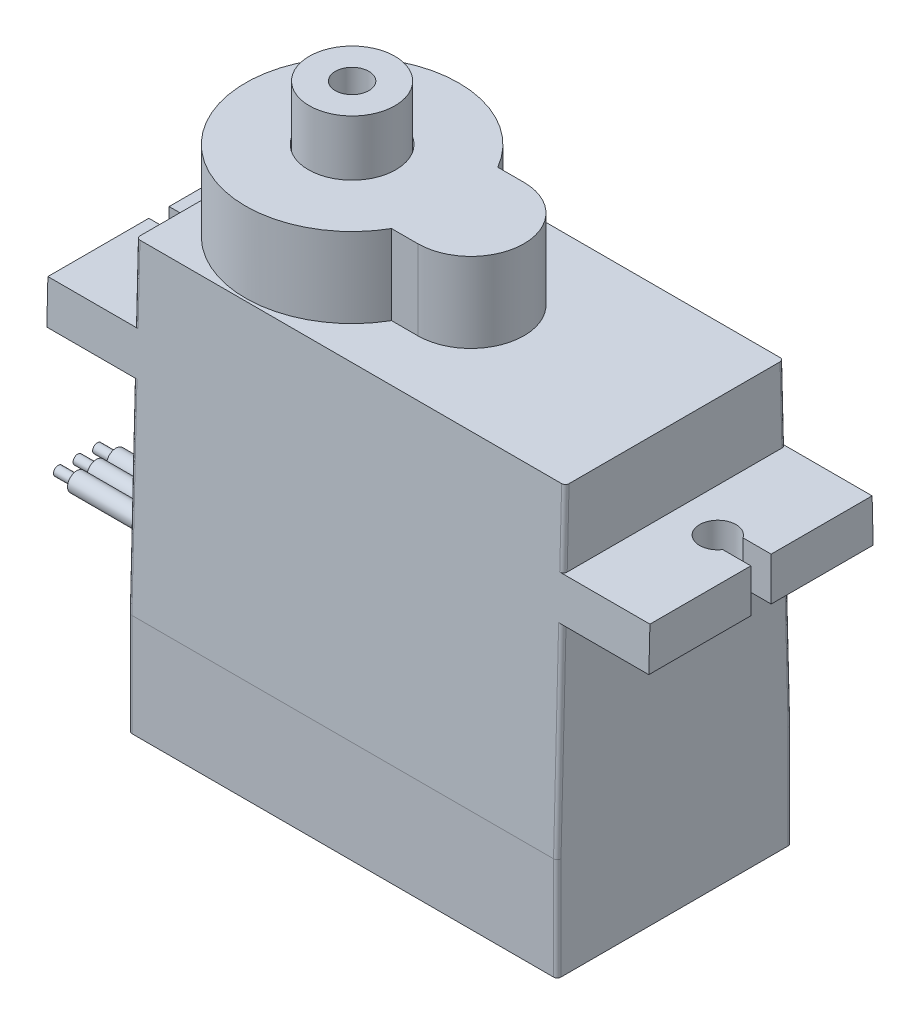
SolidWorks part; units mm, degrees
ref_plane "Front Plane" through (0, 0, 0) normal (0, 0, 1) x (1, 0, 0)
ref_plane "Top Plane" through (0, 0, 0) normal (0, 1, 0) x (1, 0, 0)
ref_plane "Right Plane" through (0, 0, 0) normal (1, 0, 0) x (0, 0, -1)
ref_axis "X-Axis" through (-88.99, 0, 0) along (1, 0, 0)
ref_axis "Y-Axis" through (0, 0, -88.99) along (0, 0, 1)
ref_axis "Z-Axis" through (0, 55, 0) along (0, -1, 0)
sketch "Sketch1" plane through (0, 0, 0) normal (0, 0, 1) x (1, 0, 0)
  line L0 (0, 0) -> (0, 12.96) construction
  line L1 (-7.13, 6.38) -> (15.9, 6.38)
  line L2 (-7.13, 6.38) -> (-7.13, 2.32)
  line L3 (-7.13, -16.34) -> (15.9, -16.34)
  line L4 (15.9, 6.38) -> (15.9, 2.32)
  line L5 (15.9, 2.32) -> (20.54, 2.32)
  line L6 (-11.77, 2.32) -> (-7.13, 2.32)
  line L7 (-11.77, 2.32) -> (-11.77, 0)
  line L8 (-11.77, 0) -> (-7.13, 0)
  line L9 (20.54, 2.32) -> (20.54, 0)
  line L10 (15.9, 0) -> (20.54, 0)
  line L11 (-7.13, 0) -> (-7.13, -16.34)
  line L12 (15.9, 0) -> (15.9, -16.34)
  line L14 (15.9, 0) -> (-7.13, 0) construction
  point P3 (4.385, 0)
  dimension "D1" = 2.32
  dimension "D2" = 32.31
  dimension "D3" = 23.03
  dimension "D4" = 16.34
  dimension "D5" = 22.72
  dimension "D6" = 7.13
  dimension "D7" = 15.9
  dimension "D10" = 29.3
  dimension "D11" = 4.385
extrude "Boss-Extrude1" add sketch "Sketch1" along normal mid plane 12.59
sketch "Sketch2" plane through (0, 6.38, 0) normal (0, 1, 0) x (1, 0, 0)
  line L0 (-1.405, 0) -> (4.97, 0) construction
  line L1 (3.5602, -2.85) -> (4.97, -2.85)
  line L2 (4.97, 2.85) -> (3.5602, 2.85)
  line L3 (-1.405, 0) -> (-7.13, 0) construction
  line L4 (4.97, 0) -> (7.82, 0) construction
  line L5 (-7.13, -6.295) -> (-7.13, 6.295) construction
  arc A0 (3.5602, 2.85) -> (3.5602, -2.85) centre (-1.405, 0) ccw
  arc A1 (4.97, -2.85) -> (4.97, 2.85) centre (4.97, 0) ccw
  dimension "D1" = 11.45
  dimension "D2" = 5.7
  dimension "D3" = 14.95
extrude "Boss-Extrude2" add sketch "Sketch2" along normal blind 4.28
sketch "Sketch11" plane through (-11.77, 0, 0) normal (-1, 0, 0) x (0, 0, 1)
  line L0 (-5.86, 6.38) -> (-6.295, -10.84)
  line L1 (0, 6.38) -> (-6.295, 6.38) construction
  line L2 (6.295, -16.34) -> (-6.295, -16.34) construction
  line L3 (-6.295, 0) -> (-6.295, -16.34) construction
  line L4 (-5.86, 6.38) -> (-6.295, 6.38)
  line L5 (-6.295, 6.38) -> (-6.295, -10.84)
  dimension "D1" = 5.86
  dimension "D2" = 5.5
extrude "Cut-Extrude4" cut sketch "Sketch11" against normal through all
mirror "Mirror1" about plane through (0, 0, 0) normal (0, 0, 1) of "Cut-Extrude4"
sketch "Sketch4" plane through (0, 0, 0) normal (0, 1, 0) x (1, 0, 0)
  line L0 (-7.13, 0) -> (-9.45, 0) construction
  line L1 (-11.77, -5.9626) -> (-11.77, 5.9626) construction
  line L2 (-10.2585, 0.545) -> (-11.77, 0.545)
  line L3 (-10.2585, 0.545) -> (-10.2585, -0.545)
  line L4 (-10.2585, -0.545) -> (-11.77, -0.545)
  line L5 (-11.77, 0.545) -> (-11.77, -0.545)
  line L8 (-9.45, 0) -> (-10.2585, 0) construction
  line L9 (-9.45, 0) -> (-11.77, 0) construction
  arc A0 (3.5602, 2.85) -> (3.5602, -2.85) centre (-1.405, 0) ccw construction
  circle A1 centre (-9.45, 0) radius 0.975
  dimension "D1" = 1.09
  dimension "D2" = 1.95
extrude "Cut-Extrude1" cut sketch "Sketch4" along normal through all contours A1 | L4 L5 L2 L3
sketch "Sketch14" plane through (0, 0.152, 6.0173) normal (0, 0.0253, 0.9997) x (1, 0, 0)
  line L0 (4.385, -10.9955) -> (-7.13, -10.9955) construction
  line L1 (15.9, -10.9955) -> (-7.13, -10.9955) construction
ref_plane "Plane1" through (4.385, -10.84, 6.295) normal (-1, 0, 0) x (0, 0, 1)
mirror "Mirror2" about plane through (4.385, -10.84, 6.295) normal (-1, 0, 0) of "Cut-Extrude1"
sketch "Sketch5" plane through (0, -16.34, 0) normal (0, -1, 0) x (1, 0, 0)
  line L0 (15.9, 6.295) -> (-7.13, -6.295) construction
  line L17 (-5.49, 4.35) -> (14.26, 4.35) construction
  line L18 (-5.49, 4.35) -> (-5.49, -4.35) construction
  line L19 (-5.49, -4.35) -> (14.26, -4.35) construction
  line L20 (14.26, 4.35) -> (14.26, -4.35) construction
  line L21 (-5.49, 4.35) -> (14.26, -4.35) construction
  circle A0 centre (-5.49, 4.35) radius 1
  circle A1 centre (-5.49, -4.35) radius 1
  circle A2 centre (14.26, -4.35) radius 1
  circle A3 centre (14.26, 4.35) radius 1
  circle A4 centre (-5.49, 4.35) radius 0.975
  circle A5 centre (-5.49, -4.35) radius 0.975
  circle A6 centre (14.26, -4.35) radius 0.975
  circle A7 centre (14.26, 4.35) radius 0.975
  point P36 (4.385, 0)
  dimension "D1" = 0.025
  dimension "D4" = 1.95
  dimension "D5" = 19.75
  dimension "D6" = 8.7
extrude "Cut-Extrude2" cut sketch "Sketch5" against normal blind 1
sketch "Sketch6" plane through (-7.13, 0, 0) normal (-1, 0, 0) x (0, 0, 1)
  line L0 (-1.05, -11.34) -> (1.05, -11.34) construction
  line L1 (0, -11.84) -> (0, -16.34) construction
  line L3 (6.295, -16.34) -> (-6.295, -16.34) construction
  circle A0 centre (0, -11.34) radius 0.5
  circle A1 centre (1.05, -11.34) radius 0.5
  circle A2 centre (-1.05, -11.34) radius 0.5
  dimension "D3" = 1
  dimension "D1" = 4.5
  dimension "D2" = 2.1
extrude "Boss-Extrude4" add sketch "Sketch6" along normal blind 8
sketch "Sketch7" plane through (-15.13, 0, 0) normal (-1, 0, 0) x (0, 0, 1)
  circle A0 centre (0, -11.34) radius 0.25
  circle A1 centre (1.05, -11.34) radius 0.25
  circle A2 centre (-1.05, -11.34) radius 0.25
  dimension "D1" = 0.5
extrude "Boss-Extrude5" add sketch "Sketch7" along normal blind 1
sketch "Sketch3" plane through (0, 10.66, 0) normal (0, 1, 0) x (1, 0, 0)
  line L0 (4.7718, -0.52) -> (4.97, -0.52)
  line L1 (4.97, 0.52) -> (4.7718, 0.52)
  line L2 (5.49, 0) -> (7.82, 0) construction
  line L3 (-4.8, 0) -> (-7.13, 0) construction
  arc A0 (4.7718, 0.52) -> (4.7718, -0.52) centre (0, 0) ccw
  arc A1 (4.97, -0.52) -> (4.97, 0.52) centre (4.97, 0) ccw
  arc A2 (4.97, -2.85) -> (4.97, 2.85) centre (4.97, 0) ccw construction
  arc A3 (3.5602, 2.85) -> (3.5602, -2.85) centre (-1.405, 0) ccw construction
  dimension "D1" = 9.6
fillet "Fillet1" radius 0.3 4 edges at (14.26, -16.34, -5.325) (14.26, -16.34, 3.375) (-5.49, -16.34, -5.325) (-5.49, -16.34, 3.375)
fillet "Fillet3" radius 0.2 12 edges at (15.9, -13.59, -6.295) (15.9, -13.59, 6.295) (-7.13, -13.59, -6.295) (-7.13, -13.59, 6.295) (-7.13, -5.42, 6.1581) (-7.13, -5.42, -6.1581) (15.9, -5.42, 6.1581) (15.9, -5.42, -6.1581) (15.9, 4.35, -5.9113) (15.9, 4.35, 5.9113) (-7.13, 4.35, -5.9113) (-7.13, 4.35, 5.9113)
sketch "Sketch12" plane through (0, 10.66, 0) normal (0, 1, 0) x (1, 0, 0)
  circle A0 centre (-1.405, 0) radius 2.3
  circle A1 centre (-1.405, 0) radius 0.9
  dimension "D1" = 4.6
  dimension "D2" = 1.8
extrude "Boss-Extrude6" add sketch "Sketch12" along normal blind 2.95 and the other way blind 1 separate body
sketch "Sketch13" plane through (0, 13.61, 0) normal (0, 1, 0) x (1, 0, 0)
  circle A0 centre (-1.405, 0) radius 2.35
  dimension "D1" = 4.7
extrude "Cut-Extrude5" cut sketch "Sketch13" against normal blind 5
